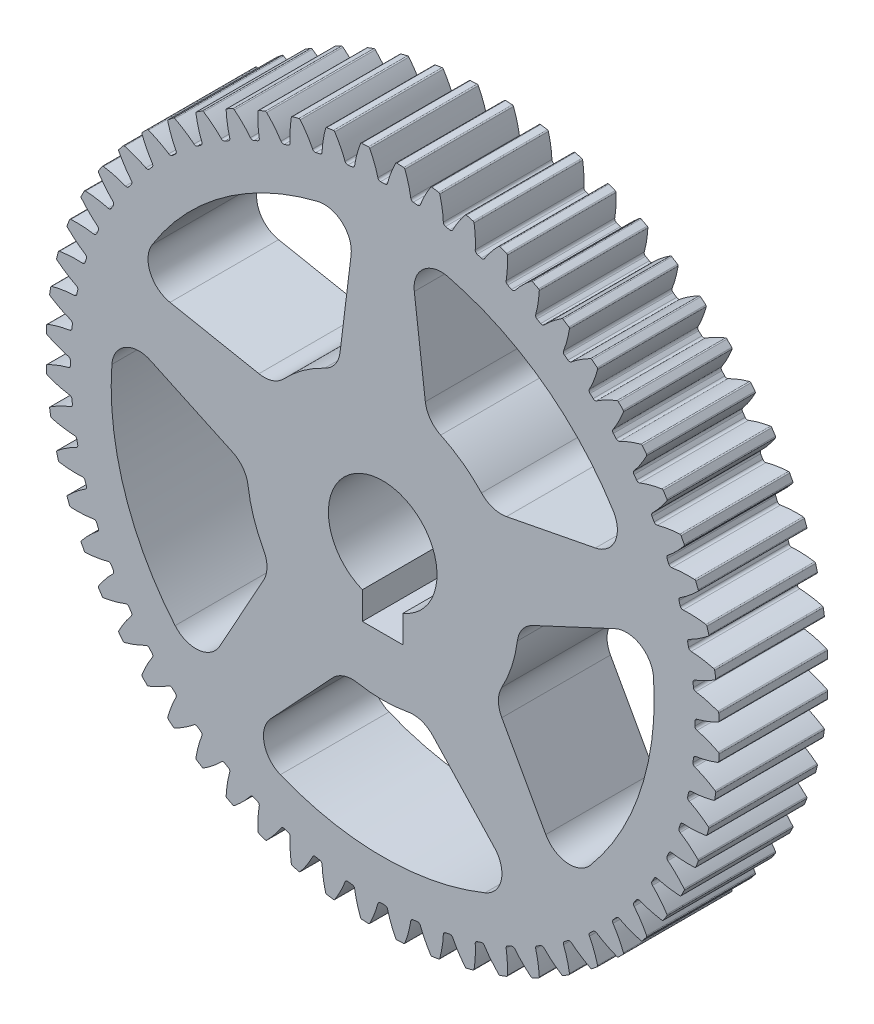
SolidWorks part; units mm, degrees
material "Alloy Steel"
ref_plane "Front" through (0, 0, 0) normal (0, 0, 1) x (1, 0, 0)
ref_plane "Top" through (0, 0, 0) normal (0, 1, 0) x (1, 0, 0)
ref_plane "Right" through (0, 0, 0) normal (1, 0, 0) x (0, 0, -1)
sketch "Sketch1" plane through (0, 0, 0) normal (0, 0, 1) x (1, 0, 0)
  circle A0 centre (0, 0) radius 39.37
  dimension "OutsideDiameter" = 78.74
extrude "Boss-Extrude1" add sketch "Sketch1" along normal blind 12.7
sketch "Sketch3" plane through (0, 0, 0) normal (0, 0, 1) x (1, 0, 0)
  line L0 (0, 0) -> (43.7181, 0) construction
  line L2 (0, 0) -> (-0.4117, 36.5102) construction
  line L3 (0, 0) -> (0.4117, 36.5102) construction
  line L4 (0.4117, 36.5102) -> (0.4037, 35.8) construction
  line L5 (0, 0) -> (0, 61.276) construction
  line L6 (-0.4117, 36.5102) -> (-0.4037, 35.8) construction
  circle A0 centre (0, 0) radius 39.37 construction
  circle A1 centre (0, 0) radius 38.1 construction
  circle A2 centre (0, 0) radius 35.8023 construction
  arc A3 (0.4117, 36.5102) -> (-0.4117, 36.5102) centre (0, 0) ccw construction
  arc A5 (1.5621, 39.339) -> (-1.5621, 39.339) centre (0, 0) ccw
  spline S0 degree 4 poles (-0.4037, 35.8) (-0.4038, 35.8056) (-0.4043, 35.8211) (-0.4059, 35.8504) (-0.4094, 35.8983) (-0.4152, 35.9593) (-0.4244, 36.0381) (-0.4372, 36.1309) (-0.4533, 36.2329) (-0.4732, 36.3438) (-0.4951, 36.4544) (-0.5188, 36.5646) (-0.5442, 36.6744) (-0.5769, 36.8074) (-0.6189, 36.9667) (-0.6721, 37.1529) (-0.7372, 37.3638) (-0.8088, 37.5787) (-0.8835, 37.7899) (-0.9639, 38.0031) (-1.0452, 38.2093) (-1.1346, 38.4233) (-1.2197, 38.6207) (-1.3206, 38.8416) (-1.4037, 39.0199) (-1.5193, 39.2547) (-1.5893, 39.3933) (-1.6733, 39.5555) (-1.7117, 39.6274) (-1.7353, 39.6717) knots 0 0 0 0 0 0.005377 0.015084 0.028532 0.04661 0.064855 0.092111 0.119476 0.146842 0.174209 0.201575 0.228941 0.256307 0.307035 0.361767 0.4165 0.471232 0.525964 0.580697 0.635429 0.690161 0.744894 0.799626 0.854358 0.909091 0.954545 1 1 1 1 1 construction
  spline S1 degree 4 poles (-0.4037, 35.8) (-0.4038, 35.8056) (-0.4043, 35.8211) (-0.4059, 35.8504) (-0.4094, 35.8983) (-0.4152, 35.9593) (-0.4244, 36.0381) (-0.4372, 36.1309) (-0.4533, 36.2329) (-0.4732, 36.3438) (-0.4951, 36.4544) (-0.5188, 36.5646) (-0.5442, 36.6744) (-0.5769, 36.8074) (-0.6189, 36.9667) (-0.6721, 37.1529) (-0.7372, 37.3638) (-0.8088, 37.5787) (-0.8835, 37.7899) (-0.9639, 38.0031) (-1.0452, 38.2093) (-1.1346, 38.4233) (-1.2197, 38.6207) (-1.3206, 38.8416) (-1.4037, 39.0199) (-1.4942, 39.2038) (-1.539, 39.2933) (-1.5621, 39.339) knots 0 0 0 0 0 0.005377 0.015084 0.028532 0.04661 0.064855 0.092111 0.119476 0.146842 0.174209 0.201575 0.228941 0.256307 0.307035 0.361767 0.4165 0.471232 0.525964 0.580697 0.635429 0.690161 0.744894 0.799626 0.854358 0.909091 0.909091 0.909091 0.909091 0.909091
  spline S2 degree 4 poles (0.4037, 35.8) (0.4038, 35.8056) (0.4043, 35.8211) (0.4059, 35.8504) (0.4094, 35.8983) (0.4152, 35.9593) (0.4244, 36.0381) (0.4372, 36.1309) (0.4533, 36.2329) (0.4732, 36.3438) (0.4951, 36.4544) (0.5188, 36.5646) (0.5442, 36.6744) (0.5769, 36.8074) (0.6189, 36.9667) (0.6721, 37.1529) (0.7372, 37.3638) (0.8088, 37.5787) (0.8835, 37.7899) (0.9639, 38.0031) (1.0452, 38.2093) (1.1346, 38.4233) (1.2197, 38.6207) (1.3206, 38.8416) (1.4037, 39.0199) (1.5193, 39.2547) (1.5893, 39.3933) (1.6733, 39.5555) (1.7117, 39.6274) (1.7353, 39.6717) knots 0 0 0 0 0 0.005377 0.015084 0.028532 0.04661 0.064855 0.092111 0.119476 0.146842 0.174209 0.201575 0.228941 0.256307 0.307035 0.361767 0.4165 0.471232 0.525964 0.580697 0.635429 0.690161 0.744894 0.799626 0.854358 0.909091 0.954545 1 1 1 1 1 construction
  spline S3 degree 4 poles (0.4037, 35.8) (0.4038, 35.8056) (0.4043, 35.8211) (0.4059, 35.8504) (0.4094, 35.8983) (0.4152, 35.9593) (0.4244, 36.0381) (0.4372, 36.1309) (0.4533, 36.2329) (0.4732, 36.3438) (0.4951, 36.4544) (0.5188, 36.5646) (0.5442, 36.6744) (0.5769, 36.8074) (0.6189, 36.9667) (0.6721, 37.1529) (0.7372, 37.3638) (0.8088, 37.5787) (0.8835, 37.7899) (0.9639, 38.0031) (1.0452, 38.2093) (1.1346, 38.4233) (1.2197, 38.6207) (1.3206, 38.8416) (1.4037, 39.0199) (1.4942, 39.2038) (1.539, 39.2933) (1.5621, 39.339) knots 0 0 0 0 0 0.005377 0.015084 0.028532 0.04661 0.064855 0.092111 0.119476 0.146842 0.174209 0.201575 0.228941 0.256307 0.307035 0.361767 0.4165 0.471232 0.525964 0.580697 0.635429 0.690161 0.744894 0.799626 0.854358 0.909091 0.909091 0.909091 0.909091 0.909091
  dimension "OutsideDiameter" = 78.74
  dimension "PitchCircle" = 76.2
  dimension "BaseCircle" = 71.6046
  dimension "DedendumCircle" = 73.025
sketch "DCLTBC" [suppressed] plane through (0, 0, 0) normal (0, 0, 1) x (1, 0, 0)
  line L0 (0, 0) -> (41.04, 0) construction
  line L1 (-0.5882, 26.2434) -> (-0.5952, 26.5563) construction
  line L2 (0.5882, 26.2434) -> (0.5952, 26.5563) construction
  line L3 (-0.5936, 26.4814) -> (-0.5952, 26.5563)
  line L4 (0.5936, 26.4814) -> (0.5952, 26.5563)
  line L5 (0, 0) -> (0, 104.9356) construction
  circle A0 centre (0, 0) radius 28.5
  circle A1 centre (0, 0) radius 27.5 construction
  circle A2 centre (0, 0) radius 26.563 construction
  arc A3 (0.5882, 26.2434) -> (-0.5882, 26.2434) centre (0, 0) ccw construction
  arc A4 (0.3512, 26.2477) -> (-0.3512, 26.2477) centre (0, 0) ccw
  arc A5 (-0.5936, 26.4814) -> (-0.3512, 26.2477) centre (-0.3544, 26.4868) ccw
  arc A7 (0.5936, 26.4814) -> (0.3512, 26.2477) centre (0.3544, 26.4868) cw
  spline S0 degree 4 poles (-999.0854, -27.9057) (-10.5882, 25.1883) (-0.7108, 25.7707) (-0.5671, 26.1913) (-0.5985, 26.609) (-0.6016, 26.6417) (-0.6063, 26.6839) (-0.6128, 26.7337) (-0.6209, 26.7885) (-0.6307, 26.8481) (-0.6414, 26.9075) (-0.653, 26.9669) (-0.6654, 27.026) (-0.6812, 27.0976) (-0.7015, 27.1836) (-0.7271, 27.2842) (-0.7584, 27.3983) (-0.7927, 27.5147) (-0.8284, 27.6294) (-0.8667, 27.7454) (-0.9054, 27.8577) (-0.948, 27.9745) (-0.9884, 28.0824) (-1.0364, 28.2034) (-1.2469, 28.7251) (-2.0615, 30.5023) (8.679, 5.7048) (-401.0337, 945.0216) knots -0.712101 -0.712101 -0.712101 -0.712101 -0.712101 0.005377 0.015084 0.028532 0.04661 0.064855 0.092111 0.119476 0.146842 0.174209 0.201575 0.228941 0.256307 0.307035 0.361767 0.4165 0.471232 0.525964 0.580697 0.635429 0.690161 0.744894 0.799626 0.854358 1.858481 1.858481 1.858481 1.858481 1.858481 only from (-0.5952, 26.5563) to (-1.151, 28.4767) construction
  spline S1 degree 4 poles (999.0854, -27.9056) (10.5882, 25.1883) (0.7108, 25.7707) (0.5671, 26.1913) (0.5985, 26.609) (0.6016, 26.6417) (0.6063, 26.6839) (0.6128, 26.7337) (0.6209, 26.7885) (0.6307, 26.8481) (0.6414, 26.9075) (0.653, 26.9669) (0.6654, 27.026) (0.6812, 27.0976) (0.7015, 27.1836) (0.7271, 27.2842) (0.7584, 27.3983) (0.7927, 27.5147) (0.8284, 27.6294) (0.8667, 27.7454) (0.9054, 27.8577) (0.948, 27.9745) (0.9884, 28.0824) (1.0364, 28.2034) (1.2469, 28.7251) (2.0615, 30.5023) (-8.679, 5.7048) (401.0337, 945.0216) knots -0.712101 -0.712101 -0.712101 -0.712101 -0.712101 0.005377 0.015084 0.028532 0.04661 0.064855 0.092111 0.119476 0.146842 0.174209 0.201575 0.228941 0.256307 0.307035 0.361767 0.4165 0.471232 0.525964 0.580697 0.635429 0.690161 0.744894 0.799626 0.854358 1.858481 1.858481 1.858481 1.858481 1.858481 only from (0.5952, 26.5563) to (1.151, 28.4767) construction
  spline S2 degree 4 poles (-0.5952, 26.5563) (-0.5953, 26.5593) (-0.5957, 26.5676) (-0.5966, 26.5833) (-0.5985, 26.609) (-0.6016, 26.6417) (-0.6063, 26.6839) (-0.6128, 26.7337) (-0.6209, 26.7885) (-0.6307, 26.8481) (-0.6414, 26.9075) (-0.653, 26.9669) (-0.6654, 27.026) (-0.6812, 27.0976) (-0.7015, 27.1836) (-0.7271, 27.2842) (-0.7584, 27.3983) (-0.7927, 27.5147) (-0.8284, 27.6294) (-0.8667, 27.7454) (-0.9054, 27.8577) (-0.948, 27.9745) (-0.9884, 28.0824) (-1.0364, 28.2034) (-1.0758, 28.3012) (-1.1188, 28.4023) (-1.14, 28.4516) (-1.151, 28.4767) knots 0 0 0 0 0 0.005377 0.015084 0.028532 0.04661 0.064855 0.092111 0.119476 0.146842 0.174209 0.201575 0.228941 0.256307 0.307035 0.361767 0.4165 0.471232 0.525964 0.580697 0.635429 0.690161 0.744894 0.799626 0.854358 0.909091 0.909091 0.909091 0.909091 0.909091
  spline S3 degree 4 poles (0.5952, 26.5563) (0.5953, 26.5593) (0.5957, 26.5676) (0.5966, 26.5833) (0.5985, 26.609) (0.6016, 26.6417) (0.6063, 26.6839) (0.6128, 26.7337) (0.6209, 26.7885) (0.6307, 26.8481) (0.6414, 26.9075) (0.653, 26.9669) (0.6654, 27.026) (0.6812, 27.0976) (0.7015, 27.1836) (0.7271, 27.2842) (0.7584, 27.3983) (0.7927, 27.5147) (0.8284, 27.6294) (0.8667, 27.7454) (0.9054, 27.8577) (0.948, 27.9745) (0.9884, 28.0824) (1.0364, 28.2034) (1.0758, 28.3012) (1.1188, 28.4023) (1.14, 28.4516) (1.151, 28.4767) knots 0 0 0 0 0 0.005377 0.015084 0.028532 0.04661 0.064855 0.092111 0.119476 0.146842 0.174209 0.201575 0.228941 0.256307 0.307035 0.361767 0.4165 0.471232 0.525964 0.580697 0.635429 0.690161 0.744894 0.799626 0.854358 0.909091 0.909091 0.909091 0.909091 0.909091
  dimension "OutsideDiameter" = 78.74
  dimension "PitchCircle" = 76.2
  dimension "BaseCircle" = 71.6046
  dimension "D1" = 0.3238
extrude "Cut-Extrude-DCLTBC" [suppressed] cut sketch "DCLTBC" along normal through all contours L4 S3 A0 S2 L3 A5 A4 A7
fillet "Fillet-DCLTBC" [suppressed] radius 0.1619
pattern_circular "CirPattern-DCLTBC" [suppressed] count 60 over 360
sketch "DCGTBC" plane through (0, 0, 0) normal (0, 0, 1) x (1, 0, 0)
  line L0 (0, 0) -> (41.04, 0) construction
  line L5 (0, 0) -> (0, 104.9356) construction
  circle A0 centre (0, 0) radius 39.37
  circle A1 centre (0, 0) radius 38.1 construction
  circle A2 centre (0, 0) radius 35.8023 construction
  arc A3 (0.4117, 36.5102) -> (-0.4117, 36.5102) centre (0, 0) ccw construction
  arc A5 (0.2483, 36.5117) -> (0.5647, 36.7571) centre (0.2505, 36.8355) ccw
  arc A7 (-0.5647, 36.7571) -> (-0.2483, 36.5117) centre (-0.2505, 36.8355) ccw
  arc A11 (0.2483, 36.5117) -> (-0.2483, 36.5117) centre (0, 0) ccw
  spline S2 degree 4 poles (-999.6499, -2.7924) (-12.7117, 33.8816) (-0.5767, 34.6054) (-0.3619, 35.2517) (-0.4094, 35.8983) (-0.4152, 35.9593) (-0.4244, 36.0381) (-0.4372, 36.1309) (-0.4533, 36.2329) (-0.4732, 36.3438) (-0.4951, 36.4544) (-0.5188, 36.5646) (-0.5442, 36.6744) (-0.5769, 36.8074) (-0.6189, 36.9667) (-0.6721, 37.1529) (-0.7372, 37.3638) (-0.8088, 37.5787) (-0.8835, 37.7899) (-0.9639, 38.0031) (-1.0452, 38.2093) (-1.1346, 38.4233) (-1.2197, 38.6207) (-1.3206, 38.8416) (-1.7103, 39.6776) (-3.067, 42.2305) (11.3258, 13.5605) (-453.5509, 931.3527) knots -0.582806 -0.582806 -0.582806 -0.582806 -0.582806 0.005377 0.015084 0.028532 0.04661 0.064855 0.092111 0.119476 0.146842 0.174209 0.201575 0.228941 0.256307 0.307035 0.361767 0.4165 0.471232 0.525964 0.580697 0.635429 0.690161 0.744894 0.799626 0.854358 1.717039 1.717039 1.717039 1.717039 1.717039 only from (-0.4037, 35.8) to (-1.5621, 39.339) construction
  spline S3 degree 4 poles (999.6499, -2.7924) (12.7117, 33.8816) (0.5767, 34.6054) (0.3619, 35.2517) (0.4094, 35.8983) (0.4152, 35.9593) (0.4244, 36.0381) (0.4372, 36.1309) (0.4533, 36.2329) (0.4732, 36.3438) (0.4951, 36.4544) (0.5188, 36.5646) (0.5442, 36.6744) (0.5769, 36.8074) (0.6189, 36.9667) (0.6721, 37.1529) (0.7372, 37.3638) (0.8088, 37.5787) (0.8835, 37.7899) (0.9639, 38.0031) (1.0452, 38.2093) (1.1346, 38.4233) (1.2197, 38.6207) (1.3206, 38.8416) (1.7103, 39.6776) (3.067, 42.2305) (-11.3258, 13.5605) (453.5509, 931.3527) knots -0.582806 -0.582806 -0.582806 -0.582806 -0.582806 0.005377 0.015084 0.028532 0.04661 0.064855 0.092111 0.119476 0.146842 0.174209 0.201575 0.228941 0.256307 0.307035 0.361767 0.4165 0.471232 0.525964 0.580697 0.635429 0.690161 0.744894 0.799626 0.854358 1.717039 1.717039 1.717039 1.717039 1.717039 only from (0.4037, 35.8) to (1.5621, 39.339) construction
  spline S4 degree 4 poles (-0.5647, 36.7571) (-0.5698, 36.7775) (-0.5877, 36.8485) (-0.6209, 36.9737) (-0.6721, 37.1529) (-0.7372, 37.3638) (-0.8088, 37.5787) (-0.8835, 37.7899) (-0.9639, 38.0031) (-1.0452, 38.2093) (-1.1346, 38.4233) (-1.2197, 38.6207) (-1.3206, 38.8416) (-1.4037, 39.0199) (-1.4942, 39.2038) (-1.539, 39.2933) (-1.5621, 39.339) knots 0.235927 0.235927 0.235927 0.235927 0.235927 0.256307 0.307035 0.361767 0.4165 0.471232 0.525964 0.580697 0.635429 0.690161 0.744894 0.799626 0.854358 0.909091 0.909091 0.909091 0.909091 0.909091
  spline S5 degree 4 poles (0.5647, 36.7571) (0.5698, 36.7775) (0.5877, 36.8485) (0.6209, 36.9737) (0.6721, 37.1529) (0.7372, 37.3638) (0.8088, 37.5787) (0.8835, 37.7899) (0.9639, 38.0031) (1.0452, 38.2093) (1.1346, 38.4233) (1.2197, 38.6207) (1.3206, 38.8416) (1.4037, 39.0199) (1.4942, 39.2038) (1.539, 39.2933) (1.5621, 39.339) knots 0.235927 0.235927 0.235927 0.235927 0.235927 0.256307 0.307035 0.361767 0.4165 0.471232 0.525964 0.580697 0.635429 0.690161 0.744894 0.799626 0.854358 0.909091 0.909091 0.909091 0.909091 0.909091
  dimension "OutsideDiameter" = 78.74
  dimension "PitchCircle" = 76.2
  dimension "BaseCircle" = 71.6046
  dimension "D1" = 0.3238
extrude "Cut-Extrude-DCGTBC" cut sketch "DCGTBC" along normal through all contours A5 S5 A0 S4 A7 A11
fillet "Fillet-DCGTBC" radius 0.1619 2 edges at (1.5621, 39.339, 6.35) (-1.5621, 39.339, 6.35)
pattern_circular "CirPattern-DCGTBC" count 60 over 360 about axis through (0, 0, 12.7) along (0, 0, 1) of "Cut-Extrude-DCGTBC", "Fillet-DCGTBC"
sketch "Sketch4" plane through (0, 0, 12.7) normal (0, 0, 1) x (1, 0, 0)
  circle A0 centre (0, 0) radius 4.7625
  dimension "D1" = 9.525
extrude "Cut-Extrude2" cut sketch "Sketch4" against normal through all
sketch "Sketch5" plane through (0, 0, 12.7) normal (0, 0, 1) x (1, 0, 0)
  circle A0 centre (0, 0) radius 6.35
  dimension "D1" = 12.7
extrude "Cut-Extrude3" cut sketch "Sketch5" against normal through all
sketch "Sketch6" plane through (0, 0, 12.7) normal (0, 0, 1) x (1, 0, 0)
  line L0 (0, 0) -> (0, -6.35) construction
  line L1 (2.3813, -3.6043) -> (-2.3812, -3.6043)
  line L2 (2.3813, -3.6043) -> (2.3813, -9.0957)
  line L3 (2.3813, -9.0957) -> (-2.3812, -9.0957)
  line L4 (-2.3812, -3.6043) -> (-2.3812, -9.0957)
  line L5 (2.3813, -3.6043) -> (-2.3812, -9.0957) construction
  line L6 (2.3813, -9.0957) -> (-2.3812, -3.6043) construction
  circle A0 centre (0, 0) radius 6.35 construction
  point P0 (0, -6.35)
  dimension "D1" = 4.7625
  dimension "D2" = 5.4915
extrude "Cut-Extrude4" cut sketch "Sketch6" against normal through all
sketch "Sketch7" plane through (0, 0, 12.7) normal (0, 0, 1) x (1, 0, 0)
  line L0 (0, 0) -> (0, 31.75) construction
  line L1 (-3.175, 31.5909) -> (-5.2127, 14.9948)
  line L2 (3.175, 31.5909) -> (5.2127, 14.9948)
  line L3 (29.0636, 12.7817) -> (12.65, 9.5913)
  line L4 (31.0258, 6.7425) -> (15.8717, -0.324)
  line L5 (21.1373, -23.6913) -> (13.0309, -9.067)
  line L6 (16, -27.4238) -> (4.5965, -15.195)
  line L7 (-16, -27.4238) -> (-4.5965, -15.195)
  line L8 (-21.1373, -23.6913) -> (-13.0309, -9.067)
  line L9 (-31.0258, 6.7425) -> (-15.8717, -0.324)
  line L10 (-29.0636, 12.7817) -> (-12.65, 9.5913)
  circle A0 centre (0, 0) radius 15.875
  circle A1 centre (0, 0) radius 31.75
  point P28 (0, 0)
  dimension "D1" = 31.75
  dimension "D2" = 63.5
  dimension "D3" = 7
  dimension "D4" = 6.35
  dimension "D5" = 5
extrude "Cut-Extrude5" cut sketch "Sketch7" against normal through all contours L1 A1 L10 A0 | L3 A1 L2 A0 | L5 A1 L4 A0 | L7 A1 L6 A0 | L9 A1 L8 A0
fillet "Fillet1" radius 3.175 20 edges at (-4.5965, -15.195, 6.35) (4.5965, -15.195, 6.35) (16, -27.4238, 6.35) (-16, -27.4238, 6.35) (31.0258, 6.7425, 6.35) (21.1373, -23.6913, 6.35) (13.0309, -9.067, 6.35) (15.8717, -0.324, 6.35) (12.65, 9.5913, 6.35) (5.2127, 14.9948, 6.35) (3.175, 31.5909, 6.35) (29.0636, 12.7817, 6.35) (-15.8717, -0.324, 6.35) (-13.0309, -9.067, 6.35) (-31.0258, 6.7425, 6.35) (-21.1373, -23.6913, 6.35) (-3.175, 31.5909, 6.35) (-5.2127, 14.9948, 6.35) (-12.65, 9.5913, 6.35) (-29.0636, 12.7817, 6.35)
equation "\"DiametralPitch\"= 20'Diametral Pitch"
equation "\"NumTeeth\"= 60'Number of Teeth"
equation "\"PressureAngle\"= 20deg'Pressure Angle"
equation "\"Addendum\"= 1 / \"DiametralPitch\"'Addendum"
equation "\"Dedendum\"= 1.25 / \"DiametralPitch\"'Dedendum"
equation "\"WorkingDepth\"= 2 / \"DiametralPitch\"'Working Depth - here for REF (Not used in building model)"
equation "\"WholeDepth\"= 2.25 / \"DiametralPitch\"'Whole Depth - here for REF (Not used in building model)"
equation "\"Clearance\"= .19 / \"DiametralPitch\"'Clearance"
equation "\"CircularPitch\"= pi / \"DiametralPitch\"'Circular Pitch - here for REF (Not used in building model)"
equation "\"PitchCircle\"= \"NumTeeth\" / \"DiametralPitch\"'Pitch Circle - or - Pitch Diameter"
equation "\"OutsideDiameter\"= ( \"NumTeeth\" + 2 ) / \"DiametralPitch\"'Outside Diameter"
equation "\"Fillet\"= \"Clearance\" * cos ( \"PressureAngle\" ) * tan ( ( 90 + \"PressureAngle\" ) / 2 )'Fillet"
equation "\"AddendumCircle\"= \"PitchCircle\" + ( 2 * \"Addendum\" )'Addendum Circle - or - Addendum Diameter"
equation "\"DedendumCircle\"= \"PitchCircle\" - ( 2 * \"Dedendum\" )'Dedendum Circle - or - Dedendum Diameter"
equation "\"BaseCircle\"= \"PitchCircle\" * cos ( \"PressureAngle\" )'Base Circle - Base Diameter"
equation "\"PitchAngle\"= 360deg / \"NumTeeth\"'Pitch Angle"
equation "\"Alpha\"= sqr ( \"PitchCircle\" ^ 2 - \"BaseCircle\" ^ 2 ) / \"BaseCircle\" * 180 / PI - \"PressureAngle\"'Alpha - Used for Calculating Beta"
equation "\"Beta\"= ( \"PitchAngle\" / 4 - ( \"Alpha\" - 90 ) )'Beta - Used in definition of the parameters for the parametric equation driven curve"
equation "\"Gamma\"= ( \"PitchAngle\" / 4 - ( \"Alpha\" + 90 ) )'Gamma - Used in definition of the parameters for the parametric equation driven curve"
equation "\"Phi\"= sqr ( ( \"AddendumCircle\" / 2 ) ^ 2 - ( \"BaseCircle\" / 2 ) ^ 2 ) / ( \"BaseCircle\" / 2 )'Phi - Used in definition of the parameters for the parametric equation driven curve"
equation "\"DCGTBC\"= iif ( ( \"DedendumCircle\" + ( \"Fillet\" * 2 ) ) > \"BaseCircle\" , \"unsuppressed\" , \"suppressed\" )'if Dedendum Circle +2X Fillet IS GREATER THAN BaseCircle THEN Unsuppress OR Suppress FEATURE"
equation "\"DCLTBC\"= iif ( ( \"DedendumCircle\" + ( \"Fillet\" * 2 ) ) > \"BaseCircle\" , \"suppressed\" , \"unsuppressed\" )'if Dedendum Circle +2X Fillet IS GREATER THAN BaseCircle THEN Suppress OR Unsuppress FEATURE"
equation "\"Cut-Extrude-DCGTBC\"= iif ( ( \"DedendumCircle\" + ( \"Fillet\" * 2 ) ) > \"BaseCircle\" , \"unsuppressed\" , \"suppressed\" )'if Dedendum Circle +2X Fillet IS GREATER THAN BaseCircle THEN UnsuppressORSuppress FEATURE"
equation "\"Cut-Extrude-DCLTBC\"= iif ( ( \"DedendumCircle\" + ( \"Fillet\" * 2 ) ) > \"BaseCircle\" , \"suppressed\" , \"unsuppressed\" )'if Dedendum Circle +2X Fillet IS GREATER THAN BaseCircle THEN SuppressORUnsuppress FEATURE"
equation "\"CirPattern-DCGTBC\"= iif ( ( \"DedendumCircle\" + ( \"Fillet\" * 2 ) ) > \"BaseCircle\" , \"unsuppressed\" , \"suppressed\" )'if Dedendum Circle +2X Fillet IS GREATER THAN \"BaseCircle\" THEN UnsuppressORSuppress FEATURE"
equation "\"CirPattern-DCLTBC\"= iif ( ( \"DedendumCircle\" + ( \"Fillet\" * 2 ) ) > \"BaseCircle\" , \"suppressed\" , \"unsuppressed\" )'if Dedendum Circle +2X Fillet IS GREATER THAN \"BaseCircle\" THEN SuppressORUnsuppress FEATURE"
equation "\"Fillet-DCGTBC\"= iif ( ( \"DedendumCircle\" + ( \"Fillet\" * 2 ) ) > \"BaseCircle\" , \"unsuppressed\" , \"suppressed\" )'if Dedendum Circle +2X Fillet IS GREATER THAN \"BaseCircle\" THEN UnsuppressORSuppress FEATURE"
equation "\"Fillet-DCLTBC\"= iif ( ( \"DedendumCircle\" + ( \"Fillet\" * 2 ) ) > \"BaseCircle\" , \"suppressed\" , \"unsuppressed\" )'if Dedendum Circle +2X Fillet IS GREATER THAN \"BaseCircle\" THEN SuppressORUnsuppress FEATURE"
equation "\"D1@CirPattern-DCGTBC\"=\"NumTeeth\""
equation "\"D1@CirPattern-DCLTBC\"=\"NumTeeth\""
equation "\"D1@DCGTBC\"=\"Fillet\""
equation "\"D1@DCLTBC\"=\"Fillet\""
equation "\"D1@Fillet-DCLTBC\"=\"Fillet\"/2"
equation "\"D1@Fillet-DCGTBC\"=\"Fillet\"/2"
